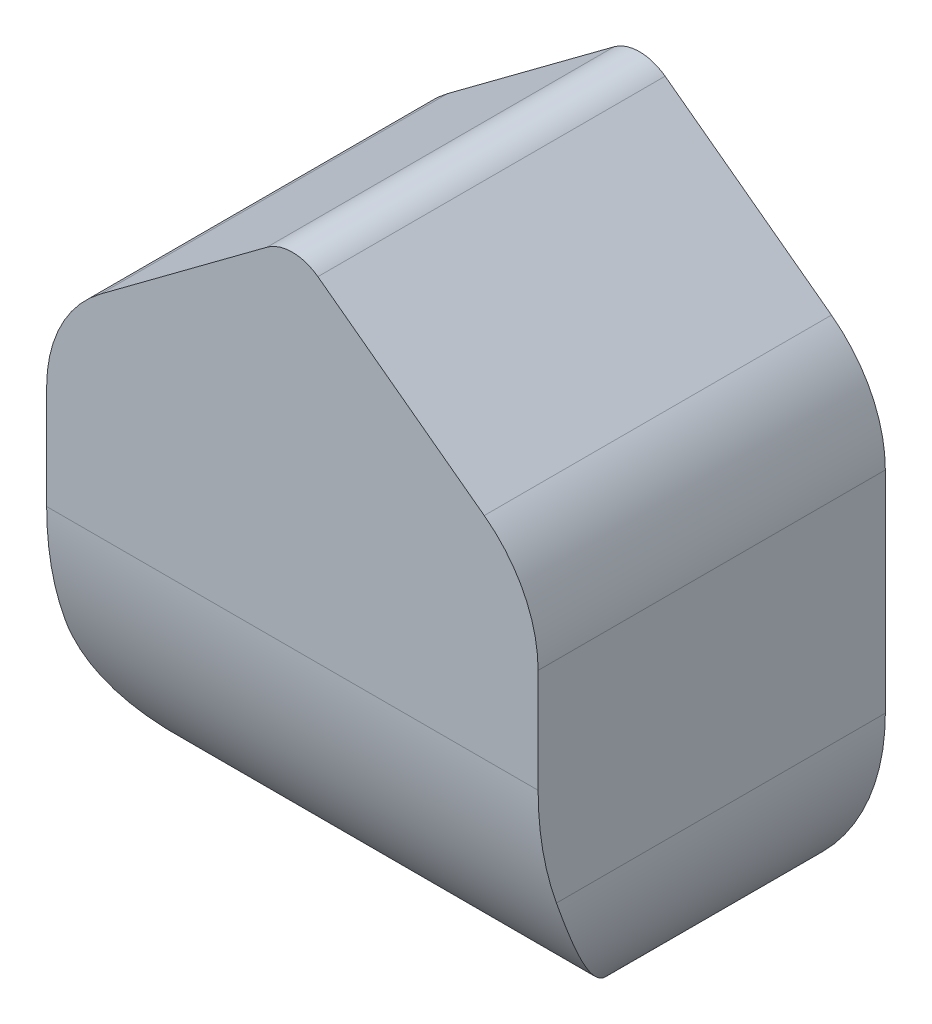
SolidWorks part; units mm, degrees
ref_plane "Front Plane" through (0, 0, 0) normal (0, 0, 1) x (1, 0, 0)
ref_plane "Top Plane" through (0, 0, 0) normal (0, 1, 0) x (1, 0, 0)
ref_plane "Right Plane" through (0, 0, 0) normal (1, 0, 0) x (0, 0, -1)
sketch "Sketch2" plane through (0, 0, 0) normal (0, 0, 1) x (1, 0, 0)
  line L0 (8, 0) -> (10.4, 0)
  line L1 (18.4, 8) -> (18.4, 15.8869)
  line L4 (0, 15.8869) -> (0, 8)
  line L7 (2.0168, 19.8994) -> (8.2454, 24.5303)
  line L8 (10.1546, 24.5303) -> (16.3832, 19.8994)
  arc A2 (8, 0) -> (0, 8) centre (8, 8) cw
  arc A3 (10.4, 0) -> (18.4, 8) centre (10.4, 8) ccw
  arc A4 (18.4, 15.8869) -> (16.3832, 19.8994) centre (13.4, 15.8869) ccw
  arc A5 (0, 15.8869) -> (2.0168, 19.8994) centre (5, 15.8869) cw
  arc A6 (8.2454, 24.5303) -> (10.1546, 24.5303) centre (9.2, 23.2462) cw
  point P11 (0, 0)
  point P14 (18.4, 0)
  dimension "D5" = 8
  dimension "D6" = 8
  dimension "D2" = 5
  dimension "D3" = 1.6
  dimension "D1" = 18.4
extrude "Boss-Extrude1" add sketch "Sketch2" along normal blind 13
sketch "Sketch3" plane through (0, 0, 13) normal (0, 0, 1) x (1, 0, 0)
  line L1 (0, 24.8462) -> (18.4, 24.8462)
  line L2 (0, 24.8462) -> (0, 0)
  line L3 (0, 0) -> (18.4, 0)
  line L4 (18.4, 24.8462) -> (18.4, 0)
fillet "Fillet1" radius 12 3 edges at (2.3431, 2.3431, 13) (9.2, 0, 13) (16.0569, 2.3431, 13)
sketch "Sketch4" plane through (0, 0, 0) normal (0, 0, -1) x (-1, 0, 0)
  line L0 (-16.9398, 18.1595) -> (-16.9398, 5.2142)
  line L1 (-16.9398, 5.2142) -> (-9.2, 0.899)
  line L2 (-9.2, 0.899) -> (-1.4602, 5.2142)
  line L3 (-1.4602, 5.2142) -> (-1.4602, 18.1595)
  line L4 (-1.4602, 18.1595) -> (-9.2, 23.2965)
  line L5 (-9.2, 23.2965) -> (-16.9398, 18.1595)
  line L6 (-16.9398, 15.043) -> (-1.4602, 15.043)
  line L7 (-16.9398, 9.2895) -> (-1.4602, 9.2895)
extrude "Cut-Extrude1" cut sketch "Sketch4" against normal blind 8 contours L0 L6 L3 L4 L5 | L7 L0 L1 L2 L3
sketch "Sketch5" plane through (0, 0, 0) normal (0, 0, -1) x (-1, 0, 0)
  circle A0 centre (-9.2, 7.64) radius 4.7168
  point P5 (-9.2, 6.4128)
extrude "Cut-Extrude2" cut sketch "Sketch5" against normal blind 8
sketch "Sketch6" plane through (0, 0, 0) normal (0, 0, -1) x (-1, 0, 0)
  line L1 (-11.4774, 15.3842) -> (-6.9226, 15.3842)
  line L2 (-11.4774, 15.3842) -> (-11.4774, 11.7706)
  line L3 (-11.4774, 11.7706) -> (-6.9226, 11.7706)
  line L4 (-6.9226, 15.3842) -> (-6.9226, 11.7706)
  line L5 (-11.4774, 15.3842) -> (-6.9226, 11.7706) construction
  line L6 (-11.4774, 11.7706) -> (-6.9226, 15.3842) construction
  arc A0 (-4.781, 9.2895) -> (-13.619, 9.2895) centre (-9.2, 7.64) ccw construction
  point P0 (-9.2, 13.5774)
extrude "Cut-Extrude3" cut sketch "Sketch6" against normal blind 8
